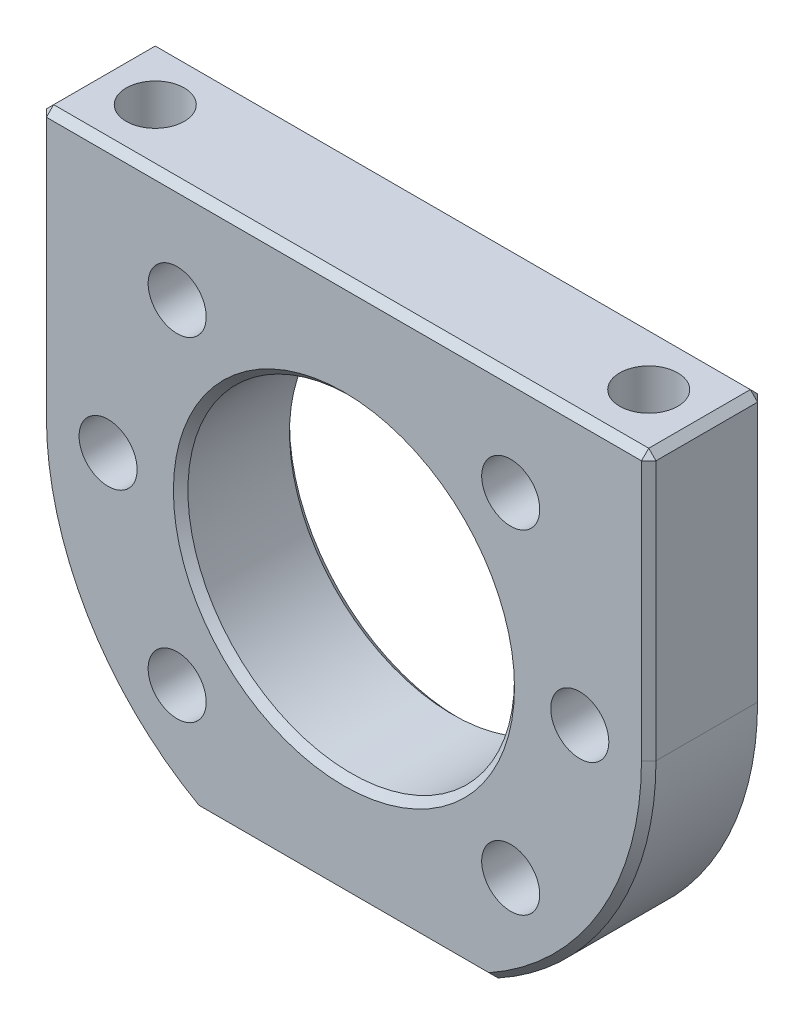
SolidWorks part; units mm, degrees
ref_plane "Front Plane" through (0, 0, 0) normal (0, 0, 1) x (1, 0, 0)
ref_plane "Top Plane" through (0, 0, 0) normal (0, 1, 0) x (1, 0, 0)
ref_plane "Right Plane" through (0, 0, 0) normal (1, 0, 0) x (0, 0, -1)
sketch "Sketch1" plane through (0, 0, 0) normal (0, 0, 1) x (1, 0, 0)
  line L0 (21, 0) -> (21, 18.4)
  line L3 (-10.1213, -18.4) -> (10.1213, -18.4)
  line L4 (-21, 0) -> (-21, 18.4)
  line L5 (-21, 18.4) -> (21, 18.4)
  arc A0 (10.1213, -18.4) -> (21, 0) centre (0, 0) ccw
  arc A1 (-21, 0) -> (-10.1213, -18.4) centre (0, 0) ccw
  dimension "D1" = 21
  dimension "D4" = 21
  dimension "D2" = 21
  dimension "D3" = 18.4
  dimension "D5" = 36.8
extrude "Boss-Extrude1" add sketch "Sketch1" along normal mid plane 8
sketch "Sketch2" plane through (0, 0, 4) normal (0, 0, 1) x (1, 0, 0)
  circle A0 centre (0, 0) radius 11.25
  dimension "D1" = 22.5
extrude "Cut-Extrude1" cut sketch "Sketch2" against normal through all
sketch "Sketch3" plane through (0, 0, 4) normal (0, 0, 1) x (1, 0, 0)
  line L0 (0, 21) -> (0, -21) construction
  line L1 (0, 0) -> (-19.8057, 19.8057) construction
  line L2 (0, 0) -> (19.0248, 19.0248) construction
  circle A0 centre (-16.25, 0) radius 2
  circle A1 centre (16.25, 0) radius 2
  circle A2 centre (0, 0) radius 16.25 construction
  circle A3 centre (-11.4905, 11.4905) radius 2
  circle A5 centre (11.4905, 11.4905) radius 2
  circle A6 centre (11.4905, -11.4905) radius 2
  circle A8 centre (-11.4905, -11.4905) radius 2
  dimension "D3" = 32.5
  dimension "D4" = 4
  dimension "D5" = 4
  dimension "D6" = 4
  dimension "D7" = 4
  dimension "D8" = 4
  dimension "D9" = 4
  dimension "D1" = 45
  dimension "D2" = 45
extrude "Cut-Extrude2" cut sketch "Sketch3" against normal blind 8
sketch "Sketch6" plane through (-3.375, 18.4, 0) normal (0, -1, 0) x (0, 0, -1)
  line L0 (0, -996.625) -> (0, 49003.375) construction
  circle A0 centre (0, -13.625) radius 2
  circle A1 centre (0, 20.375) radius 2
  dimension "D1" = 17
  dimension "D2" = 17
  dimension "D3" = 4
  dimension "D4" = 4
extrude "Cut-Extrude3" cut sketch "Sketch6" along normal blind 8
chamfer "Chamfer1" distance 0.5 angle 45 16 edges at (11.25, 0, -4) (21, 18.4, 0) (-21, 9.2, 4) (-18.0769, -10.6877, 4) (0, -18.4, 4) (18.0769, -10.6877, 4) (21, 9.2, 4) (0, 18.4, 4) (-21, 18.4, 0) (-21, 9.2, -4) (-18.0769, -10.6877, -4) (0, -18.4, -4) (18.0769, -10.6877, -4) (21, 9.2, -4) (0, 18.4, -4) (11.25, 0, 4)
equation "\"D6@Sketch3\"=\"D5@Sketch3\""
equation "\"D9@Sketch3\"=\"D5@Sketch3\""
equation "\"D8@Sketch3\"=\"D5@Sketch3\""
equation "\"D7@Sketch3\"=\"D5@Sketch3\""
equation "\"D4@Sketch3\"=\"D5@Sketch3\""
equation "\"D1@Sketch6\"=34/2"
equation "\"D4@Sketch6\"=\"D3@Sketch6\""
equation "\"D3@Sketch1\"=\"D5@Sketch1\"/2"
equation "\"D2@Sketch6\"=\"D1@Sketch6\""
